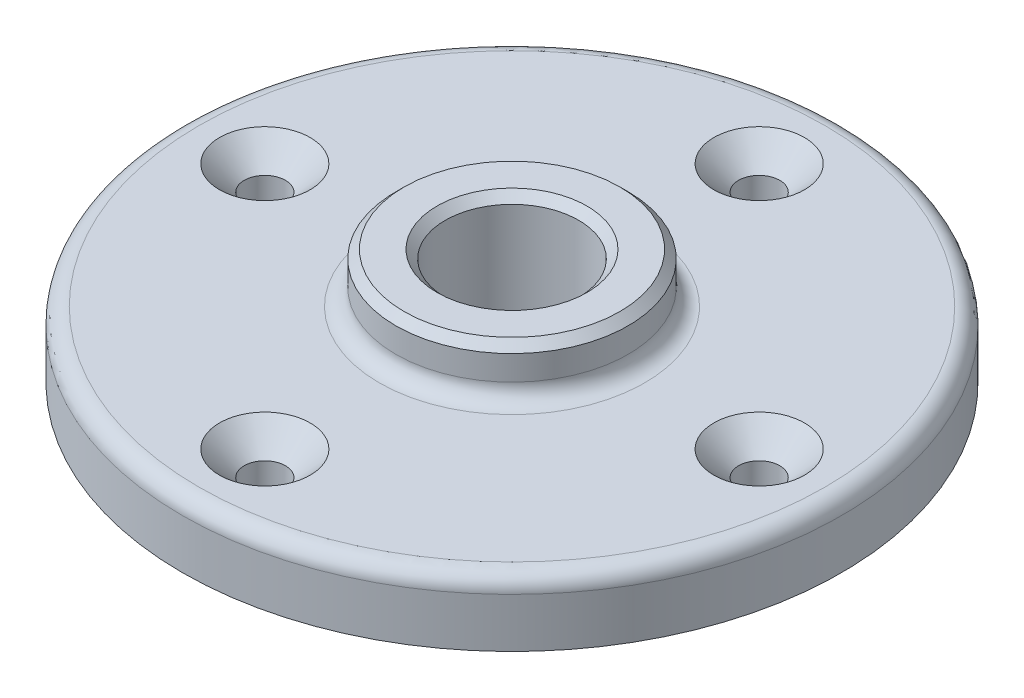
SolidWorks part; units mm, degrees
material "Nickel"
ref_plane "Front Plane" through (0, 0, 0) normal (0, 0, 1) x (1, 0, 0)
ref_plane "Top Plane" through (0, 0, 0) normal (0, 1, 0) x (1, 0, 0)
ref_plane "Right Plane" through (0, 0, 0) normal (1, 0, 0) x (0, 0, -1)
sketch "Sketch1" plane through (0, 0, 0) normal (0, 1, 0) x (1, 0, 0)
  circle A0 centre (0, 0) radius 20
  dimension "D1" = 40
extrude "Boss-Extrude1" add sketch "Sketch1" along normal blind 4
sketch "Sketch2" plane through (0, 4, 0) normal (0, 1, 0) x (1, 0, 0)
  circle A0 centre (0, 0) radius 4.05
  dimension "D1" = 8.1
extrude "Cut-Extrude1" cut sketch "Sketch2" against normal through all
sketch "Sketch3" plane through (0, 4, 0) normal (0, 1, 0) x (1, 0, 0)
  line L0 (0, 20) -> (0, 0) construction
  circle A0 centre (0, 0) radius 20 construction
  circle A1 centre (0, 15) radius 1.25
  dimension "D2" = 2.5
  dimension "D1" = 15
extrude "Cut-Extrude2" cut sketch "Sketch3" against normal through all
chamfer "Chamfer1" distance 1.5 angle 45 1 edges at (0, 4, -13.75)
ref_axis "Axis1" through (0, 0, 0) along (0, 1, 0)
pattern_circular "CirPattern1" count 4 over 360 about axis through (0, 0, 0) along (0, 1, 0) of "Cut-Extrude2", "Chamfer1"
fillet "Fillet1" radius 1 1 edges at (0, 4, 20)
sketch "Sketch4" plane through (0, 4, 0) normal (0, 1, 0) x (1, 0, 0)
  circle A0 centre (0, 0) radius 4.05 construction
  circle A1 centre (0, 0) radius 4.05
  circle A2 centre (0, 0) radius 7.05
  dimension "D1" = 3
extrude "Boss-Extrude2" add sketch "Sketch4" along normal blind 3
chamfer "Chamfer2" distance 0.5 angle 45 1 edges at (0, 7, 4.05)
fillet "Fillet2" radius 1 1 edges at (0, 4, 7.05)
chamfer "Chamfer3" distance 0.5 angle 45 1 edges at (0, 7, 7.05)
